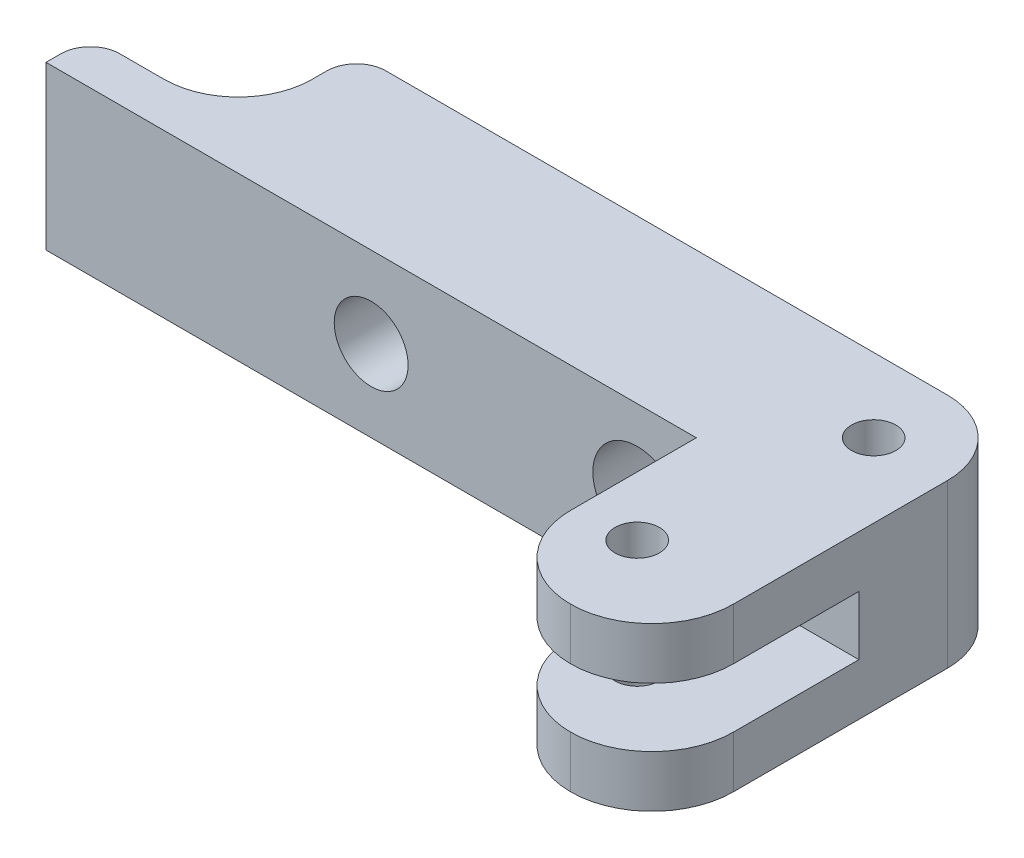
SolidWorks part; units mm, degrees
ref_plane "Front Plane" through (0, 0, 0) normal (0, 0, 1) x (1, 0, 0)
ref_plane "Top Plane" through (0, 0, 0) normal (0, 1, 0) x (1, 0, 0)
ref_plane "Right Plane" through (0, 0, 0) normal (1, 0, 0) x (0, 0, -1)
sketch "Sketch1" plane through (0, 0, 0) normal (0, 1, 0) x (1, 0, 0)
  line L0 (0, 0) -> (0, 3)
  line L1 (0, 3) -> (10, 3)
  line L2 (10, 3) -> (10, 11)
  line L3 (10, 11) -> (55, 11)
  line L4 (55, 11) -> (55, -14)
  line L5 (55, -14) -> (44, -14)
  line L6 (44, -14) -> (44, 0)
  line L7 (44, 0) -> (0, 0)
  dimension "D1" = 45
  dimension "D2" = 10
  dimension "D3" = 3
  dimension "D4" = 8
  dimension "D5" = 25
  dimension "D6" = 11
extrude "Boss-Extrude1" add sketch "Sketch1" along normal blind 11
fillet "Fillet1" radius 2 1 edges at (0, 5.5, -3) type face fillet first side face at (0, 5.5, -1.5) second side face at (5, 5.5, -3)
fillet "Fillet2" radius 5 1 edges at (10, 5.5, -3) type face fillet first side face at (6, 5.5, -3) second side face at (10, 5.5, -7)
fillet "Fillet3" radius 2 1 edges at (10, 5.5, -11) type face fillet first side face at (10, 5.5, -9.5) second side face at (32.5, 5.5, -11)
fillet "Fillet4" radius 5 1 edges at (55, 5.5, -11) type face fillet first side face at (33.5, 5.5, -11) second side face at (55, 5.5, 1.5)
fillet "Fillet5" radius 5.5 1 edges at (44, 5.5, 14) type face fillet first side face at (44, 5.5, 7) second side face at (49.5, 5.5, 14)
fillet "Fillet6" radius 5.5 1 edges at (55, 5.5, 14) type face fillet first side face at (55, 5.5, 4) second side face at (52.25, 5.5, 14)
sketch "Sketch2" plane through (44, 0, 0) normal (-1, 0, 0) x (0, 0, 1)
  line L0 (0, 11) -> (0, 0) construction
  line L1 (0, 3.5) -> (22.1979, 3.5)
  line L2 (0, 3.5) -> (0, 7.5)
  line L3 (0, 7.5) -> (22.1979, 7.5)
  line L4 (22.1979, 3.5) -> (22.1979, 7.5)
  dimension "D1" = 4
  dimension "D2" = 3.5
extrude "Cut-Extrude1" cut sketch "Sketch2" against normal blind 11
sketch "Sketch3" plane through (0, 11, 0) normal (0, 1, 0) x (1, 0, 0)
  line L0 (44, 0) -> (44, -8.5) construction
  circle A0 centre (48, -8) radius 1.5
  point P4 (44, -4.25)
  point P5 (0, 0)
  point P7 (66.5105, 1.0207)
  dimension "D3" = 3
  dimension "D1" = 4
  dimension "D2" = 6
extrude "Cut-Extrude2" cut sketch "Sketch3" against normal blind 11
sketch "Sketch4" plane through (0, 0, -11) normal (0, 0, -1) x (-1, 0, 0)
  line L0 (-55, 0) -> (-55, 11) construction
  circle A0 centre (-40, 5.5) radius 3
  point P4 (-55, 5.5)
  dimension "D1" = 6
  dimension "D2" = 15
extrude "Cut-Extrude3" cut sketch "Sketch4" against normal blind 31
sketch "Sketch5" plane through (0, 0, -11) normal (0, 0, -1) x (-1, 0, 0)
  line L0 (-10, 0) -> (-10, 11) construction
  circle A0 centre (-22, 5.5) radius 2.5
  dimension "D1" = 5
  dimension "D2" = 12
extrude "Cut-Extrude4" cut sketch "Sketch5" against normal blind 31
sketch "Sketch6" plane through (0, 11, 0) normal (0, 1, 0) x (1, 0, 0)
  circle A0 centre (50, 6) radius 1.5
extrude "Cut-Extrude5" cut sketch "Sketch6" against normal blind 31
